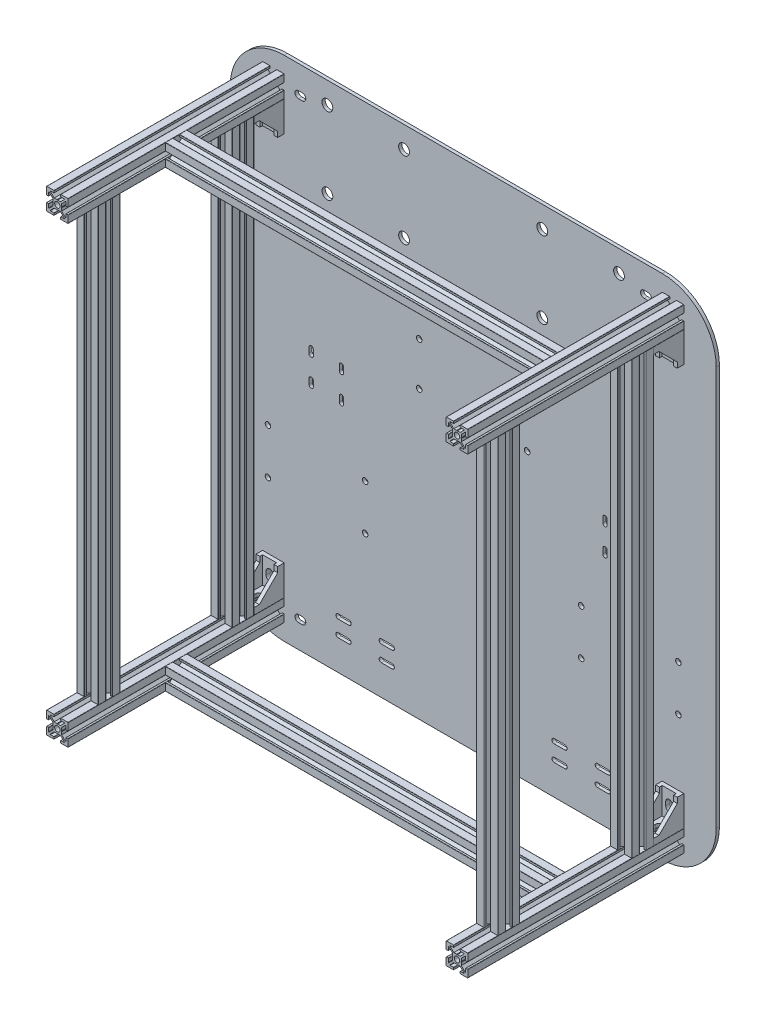
SolidWorks part; units mm, degrees
material "1060 Alloy"
ref_plane "Front Plane" through (0, 0, 0) normal (0, 0, 1) x (1, 0, 0)
ref_plane "Top Plane" through (0, 0, 0) normal (0, 1, 0) x (1, 0, 0)
ref_plane "Right Plane" through (0, 0, 0) normal (1, 0, 0) x (0, 0, -1)
sketch "Sketch1" plane through (0, 0, 0) normal (0, 0, 1) x (1, 0, 0)
  line L1 (225, 235) -> (-225, 235)
  line L2 (225, 235) -> (225, -235)
  line L3 (225, -235) -> (-225, -235)
  line L4 (-225, 235) -> (-225, -235)
  line L5 (225, 235) -> (-225, -235) construction
  line L6 (225, -235) -> (-225, 235) construction
  point P0 (0, 0)
  dimension "D1" = 470
  dimension "D2" = 450
extrude "Boss-Extrude1" add sketch "Sketch1" along normal mid plane 3
fillet "Fillet1" radius 50 4 edges at (225, -235, 0) (-225, -235, 0) (-225, 235, 0) (225, 235, 0)
sketch "Sketch3" plane through (0, 0, 1.5) normal (0, 0, 1) x (1, 0, 0)
  line L0 (-185, 210) -> (-185, -210) construction
  line L1 (185, 210) -> (185, -210) construction
  line L2 (-225, 185) -> (-225, -185) construction
  line L3 (225, -185) -> (225, 185) construction
  line L5 (-175, -220) -> (-195, -220) construction
  line L6 (-175, -220) -> (-175, -200) construction
  line L7 (-175, -200) -> (-195, -200) construction
  line L8 (-195, -220) -> (-195, -200) construction
  line L9 (-175, -220) -> (-195, -200) construction
  line L10 (-175, -200) -> (-195, -220) construction
  line L11 (195, -200) -> (175, -200) construction
  line L12 (195, -200) -> (195, -220) construction
  line L13 (195, -220) -> (175, -220) construction
  line L14 (175, -200) -> (175, -220) construction
  line L15 (195, -200) -> (175, -220) construction
  line L16 (195, -220) -> (175, -200) construction
  line L17 (-175, 200) -> (-195, 200) construction
  line L18 (-175, 200) -> (-175, 220) construction
  line L19 (-175, 220) -> (-195, 220) construction
  line L20 (-195, 200) -> (-195, 220) construction
  line L21 (-175, 200) -> (-195, 220) construction
  line L22 (-175, 220) -> (-195, 200) construction
  line L23 (195, 200) -> (175, 200) construction
  line L24 (195, 200) -> (195, 220) construction
  line L25 (195, 220) -> (175, 220) construction
  line L26 (175, 200) -> (175, 220) construction
  line L27 (195, 200) -> (175, 220) construction
  line L28 (195, 220) -> (175, 200) construction
  point P2 (-185, 0)
  point P11 (185, 0)
  dimension "D1" = 420
  dimension "D2" = 40
  dimension "D3" = 40
  dimension "D4" = 20
  dimension "D5" = 20
  dimension "D6" = 20
  dimension "D7" = 20
  dimension "D8" = 20
  dimension "D9" = 20
sketch3d "3DSketch1"
  line L0 (-185, 210, 1.5) -> (-185, 210, 201.5)
  line L1 (-185, -210, 1.5) -> (-185, -210, 201.5)
  line L2 (185, 210, 1.5) -> (185, 210, 201.5)
  line L3 (185, -210, 1.5) -> (185, -210, 201.5)
  dimension "D1" = 200
ref_plane "Plane1" through (-185, -210, 1.5) normal (0, 0, 1) x (1, 0, 0)
ref_plane "Plane2" through (-185, -210, 1.5) normal (0, 0, 1) x (1, 0, 0)
other "Vuong VUONG20X20(1)" corner treatment miter
ref_plane "Plane3" through (-185, -210, 1.5) normal (0, 0, 1) x (1, 0, 0)
sketch "Sketch11" plane through (-185, -210, 1.5) normal (0, 0, 1) x (1, 0, 0)
  line L0 (3.25, 10) -> (9.75, 10)
  line L1 (10, 9.75) -> (10, 3.25)
  line L2 (9.75, 3) -> (8.25, 3)
  line L3 (8, 3.25) -> (8, 6.3358)
  line L4 (7.5732, 6.5126) -> (4, 2.9393)
  line L5 (3, 9.75) -> (3, 8.25)
  line L6 (2.9393, 4) -> (0.3536, 4)
  line L7 (4, 2.9393) -> (4, 0.3536)
  line L8 (2.9393, -4) -> (0.3536, -4)
  line L9 (-4, 2.9393) -> (-4, 0.3536)
  line L10 (4, 4) -> (-4, -4) construction
  line L11 (4, -4) -> (-4, 4) construction
  line L12 (3.25, 8) -> (6.3358, 8)
  line L13 (6.5126, 7.5732) -> (2.9393, 4)
  line L14 (0, 0) -> (9.8325, 0) construction
  line L15 (3, -9.75) -> (3, -8.25)
  line L16 (6.5126, -7.5732) -> (2.9393, -4)
  line L17 (3.25, -8) -> (6.3358, -8)
  line L18 (7.5732, -6.5126) -> (4, -2.9393)
  line L19 (8, -3.25) -> (8, -6.3358)
  line L20 (9.75, -3) -> (8.25, -3)
  line L21 (10, -9.75) -> (10, -3.25)
  line L22 (3.25, -10) -> (9.75, -10)
  line L23 (0, 0) -> (0, 4) construction
  line L24 (-3.25, -10) -> (-9.75, -10)
  line L25 (-10, -9.75) -> (-10, -3.25)
  line L26 (-9.75, -3) -> (-8.25, -3)
  line L27 (-8, -3.25) -> (-8, -6.3358)
  line L28 (-7.5732, -6.5126) -> (-4, -2.9393)
  line L29 (-3.25, -8) -> (-6.3358, -8)
  line L30 (-6.5126, -7.5732) -> (-2.9393, -4)
  line L31 (-3, -9.75) -> (-3, -8.25)
  line L32 (-6.5126, 7.5732) -> (-2.9393, 4)
  line L33 (-3.25, 8) -> (-6.3358, 8)
  line L34 (-3, 9.75) -> (-3, 8.25)
  line L35 (-7.5732, 6.5126) -> (-4, 2.9393)
  line L36 (-8, 3.25) -> (-8, 6.3358)
  line L37 (-9.75, 3) -> (-8.25, 3)
  line L38 (-10, 9.75) -> (-10, 3.25)
  line L39 (-3.25, 10) -> (-9.75, 10)
  line L40 (-0.3536, 4) -> (0, 3.6464)
  line L41 (0, 3.6464) -> (0.3536, 4)
  line L42 (4, 0.3536) -> (3.6464, 0)
  line L43 (3.6464, 0) -> (4, -0.3536)
  line L44 (0.3536, -4) -> (0, -3.6464)
  line L45 (0, -3.6464) -> (-0.3536, -4)
  line L46 (-4, -0.3536) -> (-3.6464, 0)
  line L47 (-3.6464, 0) -> (-4, 0.3536)
  line L48 (-0.3536, -4) -> (-2.9393, -4)
  line L49 (-4, -0.3536) -> (-4, -2.9393)
  line L50 (-0.3536, 4) -> (-2.9393, 4)
  line L51 (4, -0.3536) -> (4, -2.9393)
  circle A0 centre (0, 0) radius 2.5
  arc A1 (3, 8.25) -> (3.25, 8) centre (3.25, 8.25) ccw
  arc A2 (6.3358, 8) -> (6.5126, 7.5732) centre (6.3358, 7.75) cw
  arc A3 (8, 6.3358) -> (7.5732, 6.5126) centre (7.75, 6.3358) ccw
  arc A4 (10, 3.25) -> (9.75, 3) centre (9.75, 3.25) cw
  arc A5 (8.25, 3) -> (8, 3.25) centre (8.25, 3.25) cw
  arc A6 (8, -3.25) -> (8.25, -3) centre (8.25, -3.25) cw
  arc A7 (9.75, -3) -> (10, -3.25) centre (9.75, -3.25) cw
  arc A8 (10, -9.75) -> (9.75, -10) centre (9.75, -9.75) cw
  arc A9 (7.5732, -6.5126) -> (8, -6.3358) centre (7.75, -6.3358) ccw
  arc A10 (6.5126, -7.5732) -> (6.3358, -8) centre (6.3358, -7.75) cw
  arc A11 (3, -8.25) -> (3.25, -8) centre (3.25, -8.25) cw
  arc A12 (3, -9.75) -> (3.25, -10) centre (3.25, -9.75) ccw
  arc A13 (-9.75, -10) -> (-10, -9.75) centre (-9.75, -9.75) cw
  arc A14 (-3.25, -10) -> (-3, -9.75) centre (-3.25, -9.75) ccw
  arc A15 (-3.25, -8) -> (-3, -8.25) centre (-3.25, -8.25) cw
  arc A16 (-6.3358, -8) -> (-6.5126, -7.5732) centre (-6.3358, -7.75) cw
  arc A17 (-8, -6.3358) -> (-7.5732, -6.5126) centre (-7.75, -6.3358) ccw
  arc A18 (-8.25, -3) -> (-8, -3.25) centre (-8.25, -3.25) cw
  arc A19 (-10, -3.25) -> (-9.75, -3) centre (-9.75, -3.25) cw
  arc A20 (-8, 3.25) -> (-8.25, 3) centre (-8.25, 3.25) cw
  arc A21 (-9.75, 3) -> (-10, 3.25) centre (-9.75, 3.25) cw
  arc A22 (9.75, 10) -> (10, 9.75) centre (9.75, 9.75) cw
  arc A23 (3.25, 10) -> (3, 9.75) centre (3.25, 9.75) ccw
  arc A24 (-3, 9.75) -> (-3.25, 10) centre (-3.25, 9.75) ccw
  arc A25 (-3.25, 8) -> (-3, 8.25) centre (-3.25, 8.25) ccw
  arc A26 (-7.5732, 6.5126) -> (-8, 6.3358) centre (-7.75, 6.3358) ccw
  arc A27 (-6.5126, 7.5732) -> (-6.3358, 8) centre (-6.3358, 7.75) cw
  arc A28 (-10, 9.75) -> (-9.75, 10) centre (-9.75, 9.75) cw
  point P47 (0, 0)
  point P60 (0, 0)
  point P62 (3, 8)
  point P65 (6.9393, 8)
  point P68 (8, 6.9393)
  point P71 (10, 3)
  point P74 (8, 3)
  point P77 (8, -3)
  point P80 (10, -3)
  point P83 (10, -10)
  point P86 (8, -6.9393)
  point P89 (6.9393, -8)
  point P92 (3, -8)
  point P95 (3, -10)
  point P98 (-10, -10)
  point P101 (-3, -10)
  point P104 (-3, -8)
  point P107 (-6.9393, -8)
  point P110 (-8, -6.9393)
  point P113 (-8, -3)
  point P116 (-10, -3)
  point P119 (-8, 3)
  point P122 (-10, 3)
  point P125 (10, 10)
  point P128 (3, 10)
  point P131 (-3, 10)
  point P134 (-3, 8)
  point P137 (-8, 6.9393)
  point P140 (-6.9393, 8)
  point P143 (-10, 10)
  dimension "D1" = 5
  dimension "D10" = 0.25
  dimension "D11" = 0.25
  dimension "D2" = 20
  dimension "D3" = 20
  dimension "D4" = 6
  dimension "D5" = 4
  dimension "D6" = 2
  dimension "D7" = 1.5
  dimension "D8" = 0.5
  dimension "D9" = 4
ref_plane "Plane4" through (-185, 0, 0) normal (1, 0, 0) x (0, 0, -1)
sketch "Sketch13" plane through (-185, 0, 0) normal (1, 0, 0) x (0, 0, -1)
  line L0 (-1.5, -172) -> (-5, -172)
  line L1 (-1.5, -185) -> (-1.5, 185) construction
  line L2 (-5, -172) -> (-5, -196.5)
  line L3 (-5, -196.5) -> (-29.5, -196.5)
  line L4 (-29.5, -196.5) -> (-29.5, -200)
  line L5 (-29.5, -200) -> (-1.5, -200)
  line L6 (-1.5, -185) -> (-1.5, -235) construction
  line L7 (-201.5, -200) -> (-1.5, -200) construction
  line L8 (-1.5, -172) -> (-1.5, -200)
  dimension "D1" = 28
  dimension "D2" = 28
  dimension "D3" = 3.5
extrude "Boss-Extrude2" add sketch "Sketch13" along normal mid plane 20 separate body
sketch "Sketch14" plane through (-185, 0, 0) normal (1, 0, 0) x (0, 0, -1)
  line L0 (-29.5, -196.5) -> (-29.5, -194)
  line L1 (-29.5, -194) -> (-24.5, -194)
  line L2 (-24.5, -194) -> (-7.5, -177)
  line L3 (-7.5, -177) -> (-7.5, -172)
  line L4 (-7.5, -172) -> (-5, -172)
  line L5 (-5, -172) -> (-5, -196.5)
  line L6 (-5, -196.5) -> (-29.5, -196.5)
  dimension "D1" = 135
  dimension "D2" = 2.5
  dimension "D3" = 5
extrude "Boss-Extrude3" add sketch "Sketch14" against normal blind 3.5 from surface at 10 separate body starting at face at (-175, -189.5, 12)
sketch "Sketch15" plane through (-195, 0, 0) normal (-1, 0, 0) x (0, 0, 1)
  line L7 (29.5, -194) -> (24.5, -194)
  line L8 (24.5, -194) -> (7.5, -177)
  line L9 (7.5, -177) -> (7.5, -172)
  line L10 (7.5, -172) -> (5, -172)
  line L11 (5, -172) -> (5, -196.5)
  line L12 (5, -196.5) -> (29.5, -196.5)
  line L13 (29.5, -196.5) -> (29.5, -194)
  line L14 (29.5, -194) -> (24.5, -194)
  line L15 (24.5, -194) -> (7.5, -177)
  line L16 (7.5, -177) -> (7.5, -172)
  line L17 (7.5, -172) -> (5, -172)
  line L18 (5, -172) -> (5, -196.5)
  line L19 (5, -196.5) -> (29.5, -196.5)
  line L20 (29.5, -196.5) -> (29.5, -194)
  dimension "D1" = 0
extrude "Boss-Extrude4" add sketch "Sketch15" against normal blind 3.5 separate body
sketch "Sketch16" plane through (0, 0, 5) normal (0, 0, 1) x (1, 0, 0)
  line L0 (-185, -183.25) -> (-185, -186.75) construction
  line L1 (-181.75, -183.25) -> (-181.75, -186.75)
  line L2 (-188.25, -183.25) -> (-188.25, -186.75)
  line L3 (-175, -172) -> (-195, -172) construction
  line L9 (-175, -200) -> (-195, -200) construction
  arc A0 (-181.75, -183.25) -> (-188.25, -183.25) centre (-185, -183.25) ccw
  arc A1 (-188.25, -186.75) -> (-181.75, -186.75) centre (-185, -186.75) ccw
  point P2 (-185, -185)
  point P10 (-185, -172)
  dimension "D1" = 3.25
  dimension "D2" = 10
  dimension "D3" = 10
extrude "Cut-Extrude2" cut sketch "Sketch16" against normal blind 23.5
sketch "Sketch18" plane through (0, -196.5, 0) normal (0, 1, 0) x (1, 0, 0)
  line L0 (-185, -14.75) -> (-185, -19.75) construction
  line L1 (-185, -1.5) -> (-185, -201.5) construction
  line L2 (-182, -14.75) -> (-182, -19.75)
  line L3 (-188, -14.75) -> (-188, -19.75)
  line L5 (-178.5, -5) -> (-178.5, -29.5) construction
  arc A0 (-182, -14.75) -> (-188, -14.75) centre (-185, -14.75) ccw
  arc A1 (-188, -19.75) -> (-182, -19.75) centre (-185, -19.75) ccw
  point P4 (-185, -17.25)
  point P9 (-185, -11.75)
  point P10 (-185, -22.75)
  point P13 (-178.5, -17.25)
  dimension "D1" = 3
  dimension "D2" = 11
extrude "Cut-Extrude3" cut sketch "Sketch18" against normal up to next (3.5 mm away)
combine bodies "Combine1" operation type add bodies to combine 108 112 109
mirror "Mirror1" about plane through (0, 0, 0) normal (0, 1, 0) of bodies 113
mirror "Mirror2" about plane through (0, 0, 0) normal (1, 0, 0) of bodies 113 114
sketch3d "3DSketch4"
  line L0 (-185, 200, 39.5) -> (-185, -200, 39.5)
  line L1 (-185, 210, 1.5) -> (-185, 210, 201.5) construction
  line L2 (-185, -210, 1.5) -> (-185, -210, 201.5) construction
  line L3 (-185, 200, 163.5) -> (-185, -200, 163.5)
  line L4 (185, -200, 163.5) -> (185, 200, 163.5)
  line L5 (185, -210, 1.5) -> (185, -210, 201.5) construction
  line L6 (185, 210, 1.5) -> (185, 210, 201.5) construction
  line L7 (-185, 200, 39.5) -> (-185, 210, 39.5) construction
  line L8 (175, 210, 101.5) -> (-175, 210, 101.5)
  line L9 (175, -210, 101.5) -> (-175, -210, 101.5)
  line L10 (185, -210, 101.5) -> (175, -210, 101.5) construction
  line L11 (-175, 210, 101.5) -> (-185, 210, 101.5) construction
  line L12 (-185, -200, 39.5) -> (-185, -210, 39.5) construction
  line L13 (175, 210, 101.5) -> (185, 210, 101.5) construction
  line L14 (185, -200, 39.5) -> (185, 200, 39.5)
  line L15 (185, 200, 39.5) -> (185, 210, 39.5) construction
  line L16 (185, -200, 39.5) -> (185, -210, 39.5) construction
  line L17 (185, -200, 163.5) -> (185, -210, 163.5) construction
  line L18 (-185, -200, 163.5) -> (-185, -210, 163.5) construction
  point P9 (-185, 210, 101.5)
  dimension "D1" = 38
  dimension "D2" = 38
  dimension "D3" = 38
  dimension "D4" = 38
other "Vuong VUONG20X20(2)" corner treatment miter
ref_plane "Plane6" through (175, -210, 101.5) normal (-1, 0, 0) x (0, 0, 1)
sketch "Sketch111" plane through (175, -210, 101.5) normal (-1, 0, 0) x (0, 0, 1)
  line L0 (3.25, 10) -> (9.75, 10)
  line L1 (10, 9.75) -> (10, 3.25)
  line L2 (9.75, 3) -> (8.25, 3)
  line L3 (8, 3.25) -> (8, 6.3358)
  line L4 (7.5732, 6.5126) -> (4, 2.9393)
  line L5 (3, 9.75) -> (3, 8.25)
  line L6 (2.9393, 4) -> (0.3536, 4)
  line L7 (4, 2.9393) -> (4, 0.3536)
  line L8 (2.9393, -4) -> (0.3536, -4)
  line L9 (-4, 2.9393) -> (-4, 0.3536)
  line L10 (4, 4) -> (-4, -4) construction
  line L11 (4, -4) -> (-4, 4) construction
  line L12 (3.25, 8) -> (6.3358, 8)
  line L13 (6.5126, 7.5732) -> (2.9393, 4)
  line L14 (0, 0) -> (9.8325, 0) construction
  line L15 (3, -9.75) -> (3, -8.25)
  line L16 (6.5126, -7.5732) -> (2.9393, -4)
  line L17 (3.25, -8) -> (6.3358, -8)
  line L18 (7.5732, -6.5126) -> (4, -2.9393)
  line L19 (8, -3.25) -> (8, -6.3358)
  line L20 (9.75, -3) -> (8.25, -3)
  line L21 (10, -9.75) -> (10, -3.25)
  line L22 (3.25, -10) -> (9.75, -10)
  line L23 (0, 0) -> (0, 4) construction
  line L24 (-3.25, -10) -> (-9.75, -10)
  line L25 (-10, -9.75) -> (-10, -3.25)
  line L26 (-9.75, -3) -> (-8.25, -3)
  line L27 (-8, -3.25) -> (-8, -6.3358)
  line L28 (-7.5732, -6.5126) -> (-4, -2.9393)
  line L29 (-3.25, -8) -> (-6.3358, -8)
  line L30 (-6.5126, -7.5732) -> (-2.9393, -4)
  line L31 (-3, -9.75) -> (-3, -8.25)
  line L32 (-6.5126, 7.5732) -> (-2.9393, 4)
  line L33 (-3.25, 8) -> (-6.3358, 8)
  line L34 (-3, 9.75) -> (-3, 8.25)
  line L35 (-7.5732, 6.5126) -> (-4, 2.9393)
  line L36 (-8, 3.25) -> (-8, 6.3358)
  line L37 (-9.75, 3) -> (-8.25, 3)
  line L38 (-10, 9.75) -> (-10, 3.25)
  line L39 (-3.25, 10) -> (-9.75, 10)
  line L40 (-0.3536, 4) -> (0, 3.6464)
  line L41 (0, 3.6464) -> (0.3536, 4)
  line L42 (4, 0.3536) -> (3.6464, 0)
  line L43 (3.6464, 0) -> (4, -0.3536)
  line L44 (0.3536, -4) -> (0, -3.6464)
  line L45 (0, -3.6464) -> (-0.3536, -4)
  line L46 (-4, -0.3536) -> (-3.6464, 0)
  line L47 (-3.6464, 0) -> (-4, 0.3536)
  line L48 (-0.3536, -4) -> (-2.9393, -4)
  line L49 (-4, -0.3536) -> (-4, -2.9393)
  line L50 (-0.3536, 4) -> (-2.9393, 4)
  line L51 (4, -0.3536) -> (4, -2.9393)
  circle A0 centre (0, 0) radius 2.5
  arc A1 (3, 8.25) -> (3.25, 8) centre (3.25, 8.25) ccw
  arc A2 (6.3358, 8) -> (6.5126, 7.5732) centre (6.3358, 7.75) cw
  arc A3 (8, 6.3358) -> (7.5732, 6.5126) centre (7.75, 6.3358) ccw
  arc A4 (10, 3.25) -> (9.75, 3) centre (9.75, 3.25) cw
  arc A5 (8.25, 3) -> (8, 3.25) centre (8.25, 3.25) cw
  arc A6 (8, -3.25) -> (8.25, -3) centre (8.25, -3.25) cw
  arc A7 (9.75, -3) -> (10, -3.25) centre (9.75, -3.25) cw
  arc A8 (10, -9.75) -> (9.75, -10) centre (9.75, -9.75) cw
  arc A9 (7.5732, -6.5126) -> (8, -6.3358) centre (7.75, -6.3358) ccw
  arc A10 (6.5126, -7.5732) -> (6.3358, -8) centre (6.3358, -7.75) cw
  arc A11 (3, -8.25) -> (3.25, -8) centre (3.25, -8.25) cw
  arc A12 (3, -9.75) -> (3.25, -10) centre (3.25, -9.75) ccw
  arc A13 (-9.75, -10) -> (-10, -9.75) centre (-9.75, -9.75) cw
  arc A14 (-3.25, -10) -> (-3, -9.75) centre (-3.25, -9.75) ccw
  arc A15 (-3.25, -8) -> (-3, -8.25) centre (-3.25, -8.25) cw
  arc A16 (-6.3358, -8) -> (-6.5126, -7.5732) centre (-6.3358, -7.75) cw
  arc A17 (-8, -6.3358) -> (-7.5732, -6.5126) centre (-7.75, -6.3358) ccw
  arc A18 (-8.25, -3) -> (-8, -3.25) centre (-8.25, -3.25) cw
  arc A19 (-10, -3.25) -> (-9.75, -3) centre (-9.75, -3.25) cw
  arc A20 (-8, 3.25) -> (-8.25, 3) centre (-8.25, 3.25) cw
  arc A21 (-9.75, 3) -> (-10, 3.25) centre (-9.75, 3.25) cw
  arc A22 (9.75, 10) -> (10, 9.75) centre (9.75, 9.75) cw
  arc A23 (3.25, 10) -> (3, 9.75) centre (3.25, 9.75) ccw
  arc A24 (-3, 9.75) -> (-3.25, 10) centre (-3.25, 9.75) ccw
  arc A25 (-3.25, 8) -> (-3, 8.25) centre (-3.25, 8.25) ccw
  arc A26 (-7.5732, 6.5126) -> (-8, 6.3358) centre (-7.75, 6.3358) ccw
  arc A27 (-6.5126, 7.5732) -> (-6.3358, 8) centre (-6.3358, 7.75) cw
  arc A28 (-10, 9.75) -> (-9.75, 10) centre (-9.75, 9.75) cw
  point P47 (0, 0)
  point P60 (0, 0)
  point P62 (3, 8)
  point P65 (6.9393, 8)
  point P68 (8, 6.9393)
  point P71 (10, 3)
  point P74 (8, 3)
  point P77 (8, -3)
  point P80 (10, -3)
  point P83 (10, -10)
  point P86 (8, -6.9393)
  point P89 (6.9393, -8)
  point P92 (3, -8)
  point P95 (3, -10)
  point P98 (-10, -10)
  point P101 (-3, -10)
  point P104 (-3, -8)
  point P107 (-6.9393, -8)
  point P110 (-8, -6.9393)
  point P113 (-8, -3)
  point P116 (-10, -3)
  point P119 (-8, 3)
  point P122 (-10, 3)
  point P125 (10, 10)
  point P128 (3, 10)
  point P131 (-3, 10)
  point P134 (-3, 8)
  point P137 (-8, 6.9393)
  point P140 (-6.9393, 8)
  point P143 (-10, 10)
  dimension "D1" = 5
  dimension "D10" = 0.25
  dimension "D11" = 0.25
  dimension "D2" = 20
  dimension "D3" = 20
  dimension "D4" = 6
  dimension "D5" = 4
  dimension "D6" = 2
  dimension "D7" = 1.5
  dimension "D8" = 0.5
  dimension "D9" = 4
sketch "Sketch112" plane through (-195, 0, 0) normal (-1, 0, 0) x (0, 0, 1)
  line L0 (29.75, 160) -> (29.75, 220)
  line L1 (29.75, 200) -> (29.75, -200) construction
  line L2 (29.75, 220) -> (89.75, 220)
  line L3 (201.5, 220) -> (1.5, 220) construction
  line L4 (89.75, 220) -> (89.75, 200)
  line L5 (201.5, 200) -> (1.5, 200) construction
  line L6 (89.75, 200) -> (49.5, 200)
  line L7 (49.5, 200) -> (49.5, 160)
  line L8 (49.5, 200) -> (49.5, -200) construction
  line L9 (49.5, 160) -> (29.75, 160)
  line L11 (39.5, 200) -> (39.5, -200) construction
  line L12 (1.5, 210) -> (201.5, 210) construction
  circle A0 centre (39.5, 170) radius 3
  circle A1 centre (39.5, 185) radius 3
  circle A2 centre (79.75, 210) radius 3
  circle A3 centre (64.75, 210) radius 3
  dimension "D4" = 6
  dimension "D5" = 15
  dimension "D6" = 10
  dimension "D7" = 15
  dimension "D1" = 60
  dimension "D2" = 60
  dimension "D3" = 10
extrude "Boss-Extrude5" add sketch "Sketch112" along normal blind 1 separate body
other "Save Bodies1"
sketch "Sketch114" plane through (0, 0, 1.5) normal (0, 0, 1) x (1, 0, 0)
  line L2 (-188.25, 183.25) -> (-188.25, 186.75)
  line L3 (-181.75, 186.75) -> (-181.75, 183.25)
  line L4 (0, 49.8907) -> (0, 0) construction
  line L5 (0, 0) -> (43.9289, 0) construction
  line L10 (-158.25, 210) -> (-161.75, 210) construction
  line L11 (-158.25, 206.75) -> (-161.75, 206.75)
  line L12 (-158.25, 213.25) -> (-161.75, 213.25)
  line L13 (-185, 210) -> (-160, 210) construction
  line L17 (-185, 186.75) -> (-185, 183.25) construction
  line L25 (-175, 207.0607) -> (-175, 209.6464) construction
  line L29 (-194.75, 200) -> (-188.25, 200) construction
  circle A0 centre (-185, 210) radius 2.5
  arc A1 (-181.75, 186.75) -> (-188.25, 186.75) centre (-185, 186.75) ccw
  circle A2 centre (185, 210) radius 2.5 construction
  arc A3 (-188.25, 183.25) -> (-181.75, 183.25) centre (-185, 183.25) ccw
  arc A8 (-158.25, 206.75) -> (-158.25, 213.25) centre (-158.25, 210) ccw
  arc A9 (-161.75, 213.25) -> (-161.75, 206.75) centre (-161.75, 210) ccw
  circle A16 centre (-185, -210) radius 2.5 construction
  circle A17 centre (-185, 210) radius 2.5 construction
  circle A18 centre (185, -210) radius 2.5 construction
  circle A19 centre (185, 210) radius 2.5
  circle A20 centre (-185, -210) radius 2.5
  circle A21 centre (185, -210) radius 2.5
  point P24 (-160, 210)
  dimension "D1" = 10
  dimension "D3" = 10
  dimension "D2" = 10
  dimension "D4" = 3.25
  dimension "D5" = 10
  dimension "D6" = 3.5
extrude "Cut-Extrude5" cut sketch "Sketch114" against normal through all both
mirror "Mirror3" about plane through (0, 0, 0) normal (1, 0, 0) of "Cut-Extrude5"
mirror "Mirror4" about plane through (0, 0, 0) normal (0, 1, 0) of "Mirror3", "Cut-Extrude5"
sketch "Sketch126" plane through (-196, 0, 0) normal (-1, 0, 0) x (0, 0, 1)
  line L6 (29.75, 160) -> (49.5, 160)
  line L7 (49.5, 160) -> (49.5, 200)
  line L8 (49.5, 200) -> (89.75, 200)
  line L9 (89.75, 200) -> (89.75, 220)
  line L10 (89.75, 220) -> (29.75, 220)
  line L11 (29.75, 220) -> (29.75, 160)
  line L12 (29.75, 160) -> (49.5, 160)
  line L13 (49.5, 160) -> (49.5, 200)
  line L14 (49.5, 200) -> (89.75, 200)
  line L15 (89.75, 200) -> (89.75, 220)
  line L16 (89.75, 220) -> (29.75, 220)
  line L17 (29.75, 220) -> (29.75, 160)
  dimension "D1" = 0
extrude "Cut-Extrude15" cut sketch "Sketch126" against normal up to surface (1 mm away) up to face at (-195, 216.5, 101.5)
sketch "Sketch127" plane through (0, 0, -1.5) normal (0, 0, -1) x (-1, 0, 0)
  line L0 (-137, -82) -> (-137, -120) construction
  line L1 (110, -82) -> (137, -82) construction
  line L2 (110, -82) -> (110, -120) construction
  line L3 (110, -120) -> (137, -120) construction
  line L4 (137, -82) -> (137, -120) construction
  line L5 (0, 0) -> (0, 113.9959) construction
  line L6 (-110, -120) -> (-137, -120) construction
  line L7 (-110, -82) -> (-110, -120) construction
  line L8 (-110, -82) -> (-137, -82) construction
  line L9 (-175, 235) -> (175, 235) construction
  line L17 (-225, -185) -> (-225, 185) construction
  line L18 (0, 0) -> (0, -162.2318) construction
  line L25 (225, 185) -> (225, -185) construction
  line L26 (175, -235) -> (-175, -235) construction
  line L27 (150, 7.5) -> (150, 12.5) construction
  line L28 (147.9, 7.5) -> (147.9, 12.5)
  line L29 (152.1, 7.5) -> (152.1, 12.5)
  line L30 (150, -12.5) -> (150, -17.5) construction
  line L31 (152, -12.5) -> (152, -17.5)
  line L32 (148, -12.5) -> (148, -17.5)
  line L33 (122, 12.5) -> (122, 7.5) construction
  line L34 (124, 12.5) -> (124, 7.5)
  line L35 (120, 12.5) -> (120, 7.5)
  line L36 (122, -12.5) -> (122, -17.5) construction
  line L37 (124, -12.5) -> (124, -17.5)
  line L38 (120, -12.5) -> (120, -17.5)
  line L39 (-150, 7.5) -> (-150, 12.5) construction
  line L40 (-147.9, 7.5) -> (-147.9, 12.5)
  line L41 (-152.1, 7.5) -> (-152.1, 12.5)
  line L42 (-150, -12.5) -> (-150, -17.5) construction
  line L43 (-152, -12.5) -> (-152, -17.5)
  line L44 (-148, -12.5) -> (-148, -17.5)
  line L45 (-122, 12.5) -> (-122, 7.5) construction
  line L46 (-124, 12.5) -> (-124, 7.5)
  line L47 (-120, 12.5) -> (-120, 7.5)
  line L48 (-122, -12.5) -> (-122, -17.5) construction
  line L49 (-124, -12.5) -> (-124, -17.5)
  line L50 (-120, -12.5) -> (-120, -17.5)
  line L51 (-137, -82) -> (-137, -120) construction
  line L52 (-110, -82) -> (-110, -120) construction
  line L53 (-110, -82) -> (-137, -82) construction
  line L54 (225, 185) -> (225, -185) construction
  circle A0 centre (190, -111) radius 2.55
  circle A1 centre (190, -69) radius 2.55
  arc A2 (147.9, 7.5) -> (152.1, 7.5) centre (150, 7.5) ccw
  arc A3 (152.1, 12.5) -> (147.9, 12.5) centre (150, 12.5) ccw
  arc A4 (152, -12.5) -> (148, -12.5) centre (150, -12.5) ccw
  arc A5 (148, -17.5) -> (152, -17.5) centre (150, -17.5) ccw
  arc A6 (124, 12.5) -> (120, 12.5) centre (122, 12.5) ccw
  arc A7 (120, 7.5) -> (124, 7.5) centre (122, 7.5) ccw
  arc A8 (124, -12.5) -> (120, -12.5) centre (122, -12.5) ccw
  arc A9 (120, -17.5) -> (124, -17.5) centre (122, -17.5) ccw
  arc A10 (-147.9, 7.5) -> (-152.1, 7.5) centre (-150, 7.5) cw
  arc A11 (-152.1, 12.5) -> (-147.9, 12.5) centre (-150, 12.5) cw
  arc A12 (-152, -12.5) -> (-148, -12.5) centre (-150, -12.5) cw
  arc A13 (-148, -17.5) -> (-152, -17.5) centre (-150, -17.5) cw
  arc A14 (-124, 12.5) -> (-120, 12.5) centre (-122, 12.5) cw
  arc A15 (-120, 7.5) -> (-124, 7.5) centre (-122, 7.5) cw
  arc A16 (-124, -12.5) -> (-120, -12.5) centre (-122, -12.5) cw
  arc A17 (-120, -17.5) -> (-124, -17.5) centre (-122, -17.5) cw
  circle A18 centre (-190, -69) radius 2.55
  circle A19 centre (-190, -111) radius 2.55
  circle A28 centre (-64, 215) radius 5
  circle A29 centre (-64, 144) radius 5
  circle A30 centre (-135, 144) radius 5
  circle A31 centre (-135, 215) radius 5
  circle A32 centre (135, 215) radius 5
  circle A33 centre (135, 144) radius 5
  circle A34 centre (64, 144) radius 5
  circle A35 centre (64, 215) radius 5
  circle A36 centre (100, -69) radius 2.55
  circle A37 centre (100, -111) radius 2.55
  circle A38 centre (-100, -111) radius 2.55
  circle A39 centre (-100, -69) radius 2.55
  point P37 (150, 10)
  point P46 (150, -15)
  point P53 (122, 10)
  point P58 (122, -15)
  point P67 (-150, 10)
  point P74 (-150, -15)
  point P81 (-122, 10)
  point P88 (-122, -15)
  dimension "D10" = 124
  dimension "D11" = 5.1
  dimension "D13" = 2.1
  dimension "D14" = 2
  dimension "D15" = 2
  dimension "D16" = 2
  dimension "D26" = 10
  dimension "D27" = 20
  dimension "D28" = 90
  dimension "D29" = 71
  dimension "D30" = 71
  dimension "D31" = 10
  dimension "D1" = 27
  dimension "D2" = 110
  dimension "D3" = 38
  dimension "D4" = 82
  dimension "D9" = 35
  dimension "D12" = 42
  dimension "D17" = 75
  dimension "D18" = 220
  dimension "D19" = 5
  dimension "D20" = 28
  dimension "D21" = 28
  dimension "D22" = 25
  dimension "D23" = 5
  dimension "D24" = 5
extrude "Cut-Extrude16" cut sketch "Sketch127" against normal blind 10 contours L4 L1 L2 L3 | L7 L8 L0 L6
sketch "Sketch130" plane through (0, 0, -1.5) normal (0, 0, -1) x (-1, 0, 0)
  line L0 (0, 0) -> (0, -199.472) construction
  line L1 (175, -235) -> (-175, -235) construction
  line L2 (-125, -205) -> (-115, -205) construction
  line L3 (-125, -202.9) -> (-115, -202.9)
  line L4 (-125, -207.1) -> (-115, -207.1)
  line L5 (-125, -190) -> (-115, -190) construction
  line L6 (-125, -187.9) -> (-115, -187.9)
  line L7 (-125, -192.1) -> (-115, -192.1)
  line L8 (-85, -190) -> (-75, -190) construction
  line L9 (-85, -187.9) -> (-75, -187.9)
  line L10 (-85, -192.1) -> (-75, -192.1)
  line L11 (-85, -205) -> (-75, -205) construction
  line L12 (-85, -202.9) -> (-75, -202.9)
  line L13 (-85, -207.1) -> (-75, -207.1)
  line L14 (125, -205) -> (115, -205) construction
  line L15 (125, -202.9) -> (115, -202.9)
  line L16 (125, -207.1) -> (115, -207.1)
  line L17 (125, -190) -> (115, -190) construction
  line L18 (125, -187.9) -> (115, -187.9)
  line L19 (125, -192.1) -> (115, -192.1)
  line L20 (85, -190) -> (75, -190) construction
  line L21 (85, -187.9) -> (75, -187.9)
  line L22 (85, -192.1) -> (75, -192.1)
  line L23 (85, -205) -> (75, -205) construction
  line L24 (85, -202.9) -> (75, -202.9)
  line L25 (85, -207.1) -> (75, -207.1)
  arc A0 (-125, -202.9) -> (-125, -207.1) centre (-125, -205) ccw
  circle A1 centre (120, -205) radius 2.1 construction
  arc A2 (-115, -207.1) -> (-115, -202.9) centre (-115, -205) ccw
  circle A3 centre (80, -190) radius 2.1 construction
  arc A4 (-125, -187.9) -> (-125, -192.1) centre (-125, -190) ccw
  circle A5 centre (80, -205) radius 2.1 construction
  circle A6 centre (120, -205) radius 2.1 construction
  arc A7 (-115, -192.1) -> (-115, -187.9) centre (-115, -190) ccw
  circle A8 centre (120, -190) radius 2.1 construction
  circle A9 centre (-120, -190) radius 2.1 construction
  circle A10 centre (-120, -205) radius 2.1 construction
  circle A11 centre (-80, -205) radius 2.1 construction
  circle A12 centre (-80, -190) radius 2.1 construction
  circle A13 centre (-120, -205) radius 2.1 construction
  circle A14 centre (-120, -190) radius 2.1 construction
  circle A15 centre (-120, -190) radius 2.1 construction
  arc A16 (-85, -187.9) -> (-85, -192.1) centre (-85, -190) ccw
  arc A17 (-75, -192.1) -> (-75, -187.9) centre (-75, -190) ccw
  circle A18 centre (-80, -190) radius 2.1 construction
  circle A19 centre (-80, -190) radius 2.1 construction
  arc A20 (-85, -202.9) -> (-85, -207.1) centre (-85, -205) ccw
  arc A21 (-75, -207.1) -> (-75, -202.9) centre (-75, -205) ccw
  circle A22 centre (-80, -205) radius 2.1 construction
  circle A23 centre (-80, -205) radius 2.1 construction
  arc A24 (125, -202.9) -> (125, -207.1) centre (125, -205) cw
  arc A25 (115, -207.1) -> (115, -202.9) centre (115, -205) cw
  arc A26 (125, -187.9) -> (125, -192.1) centre (125, -190) cw
  arc A27 (115, -192.1) -> (115, -187.9) centre (115, -190) cw
  arc A28 (85, -187.9) -> (85, -192.1) centre (85, -190) cw
  arc A29 (75, -192.1) -> (75, -187.9) centre (75, -190) cw
  arc A30 (85, -202.9) -> (85, -207.1) centre (85, -205) cw
  arc A31 (75, -207.1) -> (75, -202.9) centre (75, -205) cw
  circle A32 centre (80, -205) radius 2.1 construction
  circle A33 centre (80, -205) radius 2.1 construction
  circle A34 centre (80, -190) radius 2.1 construction
  circle A35 centre (80, -190) radius 2.1 construction
  circle A36 centre (120, -190) radius 2.1 construction
  circle A37 centre (120, -190) radius 2.1 construction
  circle A38 centre (120, -205) radius 2.1 construction
  circle A39 centre (80, -190) radius 2.1 construction
  circle A40 centre (80, -205) radius 2.1 construction
  circle A41 centre (120, -205) radius 2.1 construction
  circle A42 centre (120, -190) radius 2.1 construction
  point P25 (-120, -205)
  point P35 (-120, -190)
  point P46 (-80, -190)
  point P57 (-80, -205)
  point P64 (120, -205)
  point P71 (120, -190)
  point P78 (80, -190)
  point P85 (80, -205)
  dimension "D1" = 4.2
  dimension "D3" = 30
  dimension "D2" = 40
  dimension "D4" = 15
  dimension "D5" = 80
  dimension "D6" = 4.2
  dimension "D7" = 10
  dimension "D8" = 4.2
  dimension "D9" = 10
  dimension "D10" = 4.2
  dimension "D11" = 10
  dimension "D12" = 4.2
  dimension "D13" = 10
extrude "Cut-Extrude17" cut sketch "Sketch130" against normal blind 10 contours A5 | A3 | A8 | A1 | L4 A2 L3 A0 | L7 A7 L6 A4 | L10 A17 L9 A16 | L13 A21 L12 A20 | A31 L25 A30 L24 | A25 L16 A24 L15 | A27 L19 A26 L18 | A29 L22 A28 L21 | A11 | A12 | A9 | A10
sketch "Sketch131" plane through (0, 0, -1.5) normal (0, 0, -1) x (-1, 0, 0)
  line L0 (0, 147.1735) -> (0, 0) construction
  circle A0 centre (-50, 110) radius 2.6
  circle A1 centre (-50, 70) radius 2.6
  circle A2 centre (-50, 30) radius 2.6
  dimension "D1" = 5.2
  dimension "D2" = 50
  dimension "D3" = 40
  dimension "D4" = 30
  dimension "D5" = 40
extrude "Cut-Extrude18" cut sketch "Sketch131" against normal blind 10
mirror "Mirror5" about plane through (0, 0, 0) normal (1, 0, 0) of "Cut-Extrude18"
